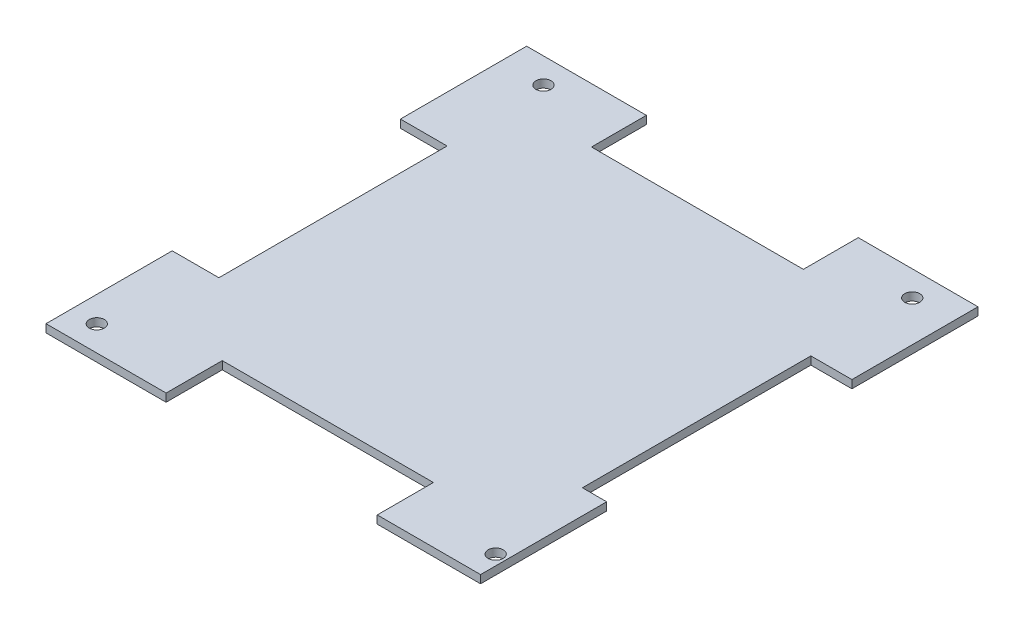
SolidWorks part; units mm, degrees
material "Custom Plastic"
ref_plane "Front Plane" through (0, 0, 0) normal (0, 0, 1) x (1, 0, 0)
ref_plane "Top Plane" through (0, 0, 0) normal (0, 1, 0) x (1, 0, 0)
ref_plane "Right Plane" through (0, 0, 0) normal (1, 0, 0) x (0, 0, -1)
sketch "Sketch2" plane through (0, 0, 0) normal (0, 1, 0) x (1, 0, 0)
  line L1 (0, 0) -> (84.57, 0)
  line L2 (0, 0) -> (0, 90.8)
  line L3 (0, 90.8) -> (84.57, 90.8)
  line L4 (84.57, 0) -> (84.57, 90.8)
extrude "Boss-Extrude1" add sketch "Sketch2" along normal blind 1.6
sketch "Sketch3" plane through (0, 1.6, 0) normal (0, 1, 0) x (1, 0, 0)
  line L3 (0, 0) -> (84.57, 0) construction
  line L4 (84.57, 90.8) -> (0, 90.8) construction
  circle A0 centre (2.5, 2.5) radius 1.5
  circle A1 centre (82.07, 2.5) radius 1.5
  circle A2 centre (5.8, 88.3) radius 1.5
  circle A3 centre (79.37, 88.3) radius 1.5
extrude "Cut-Extrude1" cut sketch "Sketch3" against normal through all
sketch "Sketch4" plane through (84.57, 0, 0) normal (1, 0, 0) x (0, 0, -1)
  line L1 (90.8, 1.6) -> (0, 1.6)
  line L2 (90.8, 1.6) -> (90.8, 0)
  line L3 (90.8, 0) -> (0, 0)
  line L4 (0, 1.6) -> (0, 0)
extrude "Boss-Extrude2" add sketch "Sketch4" along normal blind 2.88
sketch "Sketch5" plane through (0, 0, 0) normal (-1, 0, 0) x (0, 0, 1)
  line L1 (-90.8, 0) -> (0, 0)
  line L2 (-90.8, 0) -> (-90.8, 1.6)
  line L3 (-90.8, 1.6) -> (0, 1.6)
  line L4 (0, 0) -> (0, 1.6)
extrude "Boss-Extrude3" add sketch "Sketch5" along normal blind 2.59
sketch "Sketch6" plane through (0, 0, -90.8) normal (0, 0, -1) x (-1, 0, 0)
  line L1 (2.59, 0) -> (-87.45, 0)
  line L2 (2.59, 0) -> (2.59, 1.6)
  line L3 (2.59, 1.6) -> (-87.45, 1.6)
  line L4 (-87.45, 0) -> (-87.45, 1.6)
extrude "Boss-Extrude4" add sketch "Sketch6" along normal blind 2.54
sketch "Sketch7" plane through (0, 0, 0) normal (0, 0, 1) x (1, 0, 0)
  line L1 (87.45, 1.6) -> (-2.59, 1.6)
  line L2 (87.45, 1.6) -> (87.45, 0)
  line L3 (87.45, 0) -> (-2.59, 0)
  line L4 (-2.59, 1.6) -> (-2.59, 0)
extrude "Boss-Extrude5" add sketch "Sketch7" along normal blind 2.54
sketch "Sketch8" plane through (0, 1.6, 0) normal (0, 1, 0) x (1, 0, 0)
  line L0 (87.45, 93.34) -> (87.45, -2.54) construction
  line L1 (95.6363, 68.1858) -> (79.2637, 68.1858)
  line L2 (95.6363, 68.1858) -> (95.6363, 22.6142)
  line L3 (95.6363, 22.6142) -> (79.2637, 22.6142)
  line L4 (79.2637, 68.1858) -> (79.2637, 22.6142)
  line L5 (95.6363, 68.1858) -> (79.2637, 22.6142) construction
  line L6 (95.6363, 22.6142) -> (79.2637, 68.1858) construction
  line L7 (-2.59, 93.34) -> (87.45, 93.34) construction
  line L8 (63.5632, 104.2905) -> (21.2968, 104.2905)
  line L9 (63.5632, 104.2905) -> (63.5632, 82.3895)
  line L10 (63.5632, 82.3895) -> (21.2968, 82.3895)
  line L11 (21.2968, 104.2905) -> (21.2968, 82.3895)
  line L12 (63.5632, 104.2905) -> (21.2968, 82.3895) construction
  line L13 (63.5632, 82.3895) -> (21.2968, 104.2905) construction
  line L14 (-2.59, -2.54) -> (-2.59, 93.34) construction
  line L15 (6.7185, 68.1601) -> (-11.8985, 68.1601)
  line L16 (6.7185, 68.1601) -> (6.7185, 22.6399)
  line L17 (6.7185, 22.6399) -> (-11.8985, 22.6399)
  line L18 (-11.8985, 68.1601) -> (-11.8985, 22.6399)
  line L19 (6.7185, 68.1601) -> (-11.8985, 22.6399) construction
  line L20 (6.7185, 22.6399) -> (-11.8985, 68.1601) construction
  line L21 (87.45, -2.54) -> (-2.59, -2.54) construction
  line L22 (63.4894, 8.6601) -> (21.3706, 8.6601)
  line L23 (63.4894, 8.6601) -> (63.4894, -13.7401)
  line L24 (63.4894, -13.7401) -> (21.3706, -13.7401)
  line L25 (21.3706, 8.6601) -> (21.3706, -13.7401)
  line L26 (63.4894, 8.6601) -> (21.3706, -13.7401) construction
  line L27 (63.4894, -13.7401) -> (21.3706, 8.6601) construction
  point P0 (87.45, 45.4)
  point P7 (42.43, 93.34)
  point P14 (-2.59, 45.4)
  point P21 (42.43, -2.54)
extrude "Cut-Extrude2" cut sketch "Sketch8" against normal through all
sketch "Sketch9" plane through (87.45, 0, 0) normal (1, 0, 0) x (0, 0, -1)
  line L1 (-2.54, 1.6) -> (22.6142, 1.6)
  line L2 (-2.54, 1.6) -> (-2.54, 0)
  line L3 (-2.54, 0) -> (22.6142, 0)
  line L4 (22.6142, 1.6) -> (22.6142, 0)
extrude "Cut-Extrude3" cut sketch "Sketch9" against normal blind 3.35
